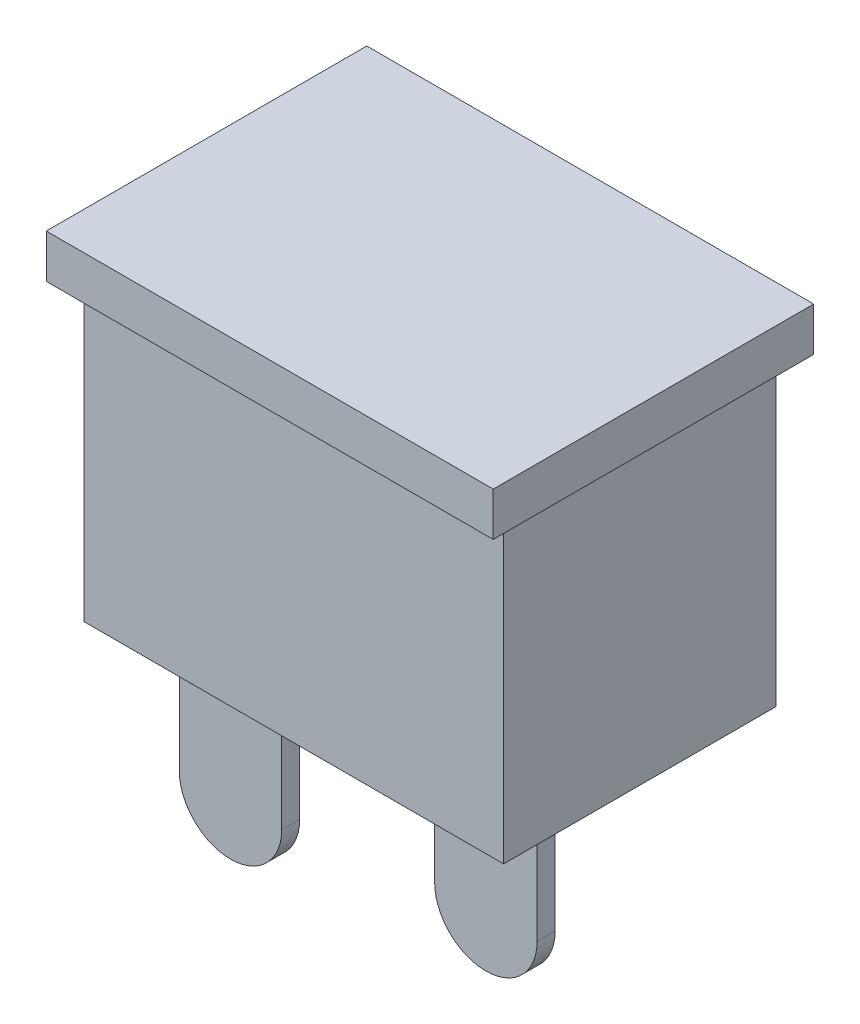
SolidWorks part; units mm, degrees
ref_plane "Front" through (0, 0, 0) normal (0, 0, 1) x (1, 0, 0)
ref_plane "Top" through (0, 0, 0) normal (0, 1, 0) x (1, 0, 0)
ref_plane "Right" through (0, 0, 0) normal (1, 0, 0) x (0, 0, -1)
sketch "Sketch1" plane through (0, 0, 0) normal (0, 1, 0) x (1, 0, 0)
  line L1 (0, 0) -> (19.558, 0)
  line L2 (0, 0) -> (0, 12.7)
  line L3 (0, 12.7) -> (19.558, 12.7)
  line L4 (19.558, 0) -> (19.558, 12.7)
  dimension "D1" = 19.558
  dimension "D2" = 12.7
extrude "Boss-Extrude1" add sketch "Sketch1" against normal blind 13.97
sketch "Sketch2" plane through (0, 0, 0) normal (0, 1, 0) x (1, 0, 0)
  line L0 (0, 12.7) -> (0, 0) construction
  line L1 (-0.635, -1.1176) -> (20.193, -1.1176)
  line L2 (-0.635, -1.1176) -> (-0.635, 13.8176)
  line L3 (-0.635, 13.8176) -> (20.193, 13.8176)
  line L4 (20.193, -1.1176) -> (20.193, 13.8176)
  line L5 (19.558, 12.7) -> (0, 12.7) construction
  point P6 (0, 6.35)
  point P7 (-0.635, 6.35)
  point P10 (9.779, 12.7)
  point P11 (9.779, 13.8176)
  dimension "D1" = 20.828
  dimension "D2" = 14.9352
extrude "Boss-Extrude2" add sketch "Sketch2" along normal blind 2.032
sketch "Sketch3" plane through (0, -13.97, 0) normal (0, -1, 0) x (1, 0, 0)
  line L0 (0, -12.7) -> (0, 0) construction
  line L1 (2.54, -2.7432) -> (7.3152, -2.7432)
  line L2 (2.54, -2.7432) -> (2.54, -1.905)
  line L3 (2.54, -1.905) -> (7.3152, -1.905)
  line L4 (7.3152, -2.7432) -> (7.3152, -1.905)
  line L5 (13.0048, -4.1783) -> (17.78, -4.1783)
  line L6 (13.0048, -4.1783) -> (13.0048, -3.3401)
  line L7 (13.0048, -3.3401) -> (17.78, -3.3401)
  line L8 (17.78, -4.1783) -> (17.78, -3.3401)
  line L9 (19.558, 0) -> (19.558, -12.7) construction
  line L10 (0, 0) -> (19.558, 0) construction
  line L11 (0, 0) -> (19.558, 0) construction
  dimension "D1" = 4.7752
  dimension "D2" = 0.8382
  dimension "D3" = 2.54
  dimension "D4" = 1.778
  dimension "D5" = 3.3401
  dimension "D6" = 1.905
extrude "Boss-Extrude3" add sketch "Sketch3" along normal blind 8.0772
fillet "Fillet1" 2 edges at (2.54, -22.0472, -2.3241) (7.3152, -22.0472, -2.3241) type full round first side face at (2.54, -18.0086, -2.3241) second side face at (7.3152, -18.0086, -2.3241) middle face at (4.9276, -22.0472, -2.3241)
fillet "Fillet2" 2 edges at (13.0048, -22.0472, -3.7592) (17.78, -22.0472, -3.7592) type full round first side face at (13.0048, -18.0086, -3.7592) second side face at (17.78, -18.0086, -3.7592) middle face at (15.3924, -22.0472, -3.7592)
